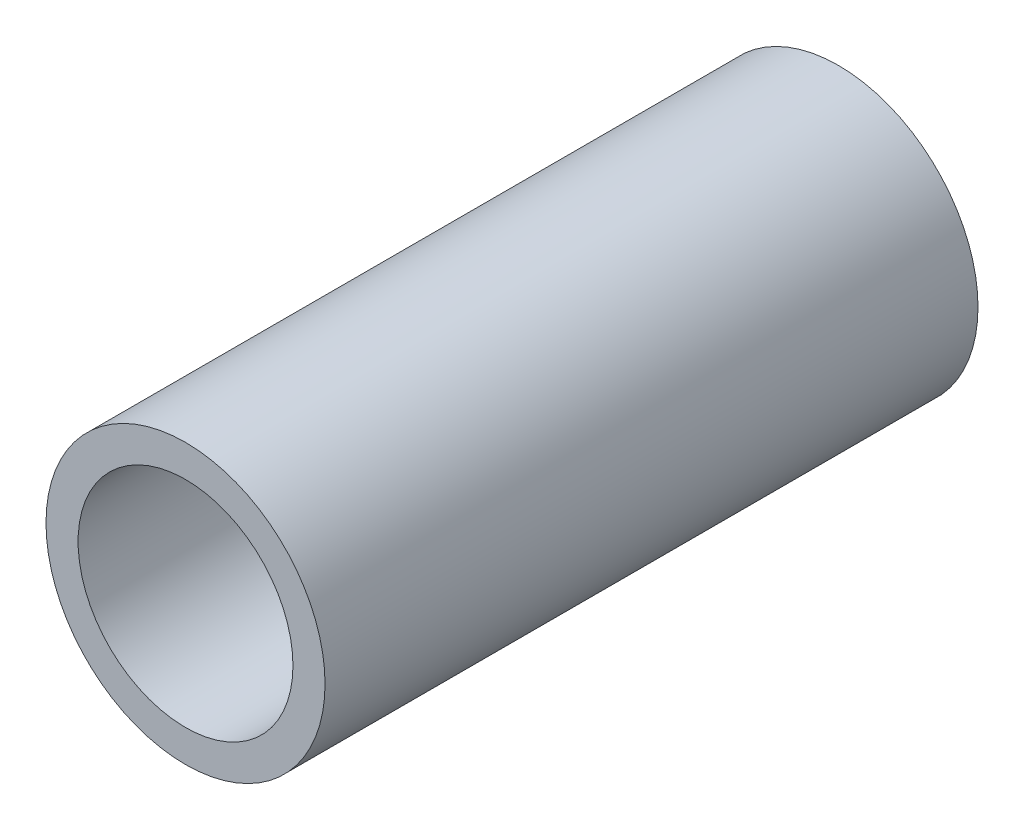
SolidWorks part; units mm, degrees
material "Delrin 2700 NC010, Low Viscosity Acetal Copolymer (SS)"
ref_plane "Front" through (0, 0, 0) normal (0, 0, 1) x (1, 0, 0)
ref_plane "Top" through (0, 0, 0) normal (0, 1, 0) x (1, 0, 0)
ref_plane "Right" through (0, 0, 0) normal (1, 0, 0) x (0, 0, -1)
sketch "Sketch1" plane through (0, 0, 0) normal (0, 0, 1) x (1, 0, 0)
  circle A0 centre (0, 0) radius 4.8895
  circle A1 centre (0, 0) radius 6.35
  dimension "D1" = 9.779
  dimension "D2" = 12.7
extrude "Boss-Extrude1" add sketch "Sketch1" along normal blind 29.718
